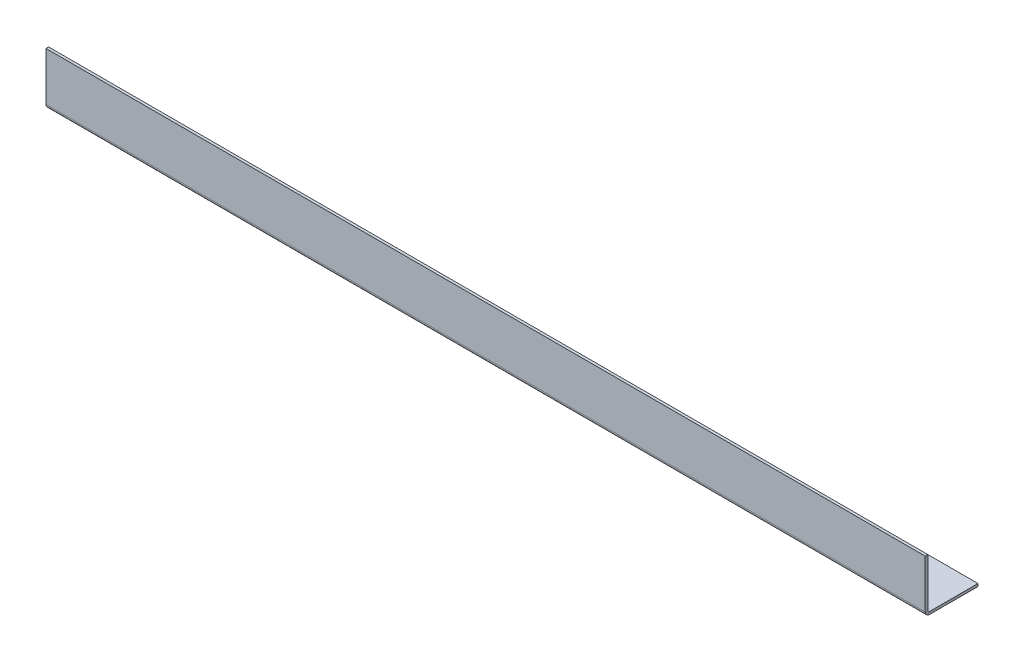
SolidWorks part; units mm, degrees
material "201 Annealed Stainless Steel (SS)"
ref_plane "Front Plane" through (0, 0, 0) normal (0, 0, 1) x (1, 0, 0)
ref_plane "Top Plane" through (0, 0, 0) normal (0, 1, 0) x (1, 0, 0)
ref_plane "Right Plane" through (0, 0, 0) normal (1, 0, 0) x (0, 0, -1)
sketch "Sketch1" plane through (0, 0, 0) normal (1, 0, 0) x (0, 0, -1)
  line L0 (0, 0) -> (0, 60)
  line L1 (0, 0) -> (60, 0)
  line L2 (60, 0) -> (60, 3)
  line L3 (60, 3) -> (3, 3)
  line L4 (3, 3) -> (3, 60)
  line L5 (3, 60) -> (0, 60)
  dimension "D1" = 60
  dimension "D2" = 60
  dimension "D3" = 3
extrude "Boss-Extrude1" add sketch "Sketch1" along normal mid plane 1000
fillet "Fillet1" radius 5 1 edges at (0, 0, 0)
